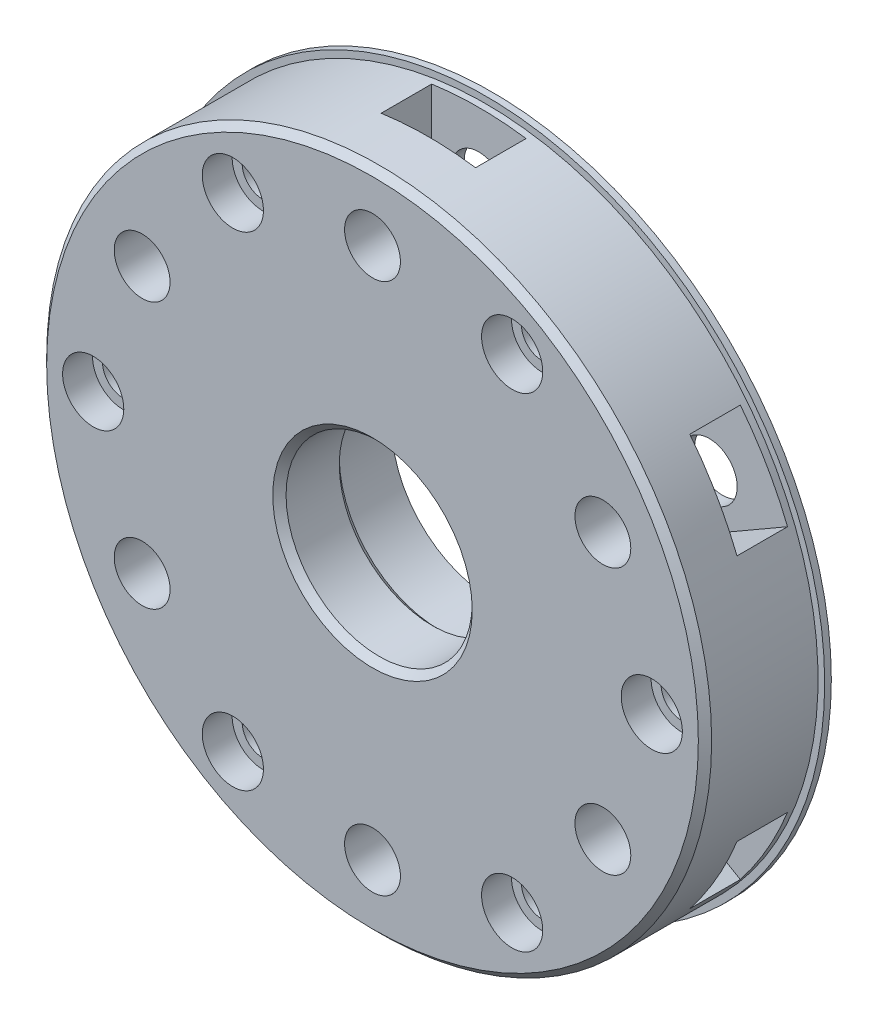
SolidWorks part; units mm, degrees
material "ABS"
ref_plane "Front Plane" through (0, 0, 0) normal (0, 0, 1) x (1, 0, 0)
ref_plane "Top Plane" through (0, 0, 0) normal (0, 1, 0) x (1, 0, 0)
ref_plane "Right Plane" through (0, 0, 0) normal (1, 0, 0) x (0, 0, -1)
sketch "Output Master Sketch" plane through (0, 0, 0) normal (0, 0, 1) x (1, 0, 0)
  circle A0 centre (0, 0) radius 21 construction
  circle A1 centre (21, 0) radius 3.05 construction
  circle A2 centre (10.5, -18.1865) radius 3.05 construction
  circle A3 centre (-10.5, -18.1865) radius 3.05 construction
  circle A4 centre (-21, 0) radius 3.05 construction
  circle A5 centre (-10.5, 18.1865) radius 3.05 construction
  circle A6 centre (10.5, 18.1865) radius 3.05 construction
  circle A7 centre (0, 0) radius 25
  point P17 (0, 0)
extrude "Boss-Extrude1" add sketch "Output Master Sketch" along normal blind 9
sketch "Sketch4" plane through (0, 0, 0) normal (0, 0, 1) x (1, 0, 0)
  circle A0 centre (21, 0) radius 3.05
  circle A1 centre (21, 0) radius 3.05 construction
  circle A2 centre (10.5, -18.1865) radius 3.05
  circle A3 centre (-10.5, -18.1865) radius 3.05
  circle A4 centre (-21, 0) radius 3.05
  circle A5 centre (-10.5, 18.1865) radius 3.05
  circle A6 centre (10.5, 18.1865) radius 3.05
  point P5 (0, 0)
  point P17 (0, 0)
  dimension "D1" = 6
extrude "Cut-Extrude1" cut sketch "Sketch4" along normal blind 4
sketch "Sketch5" plane through (0, 0, 0) normal (0, 0, -1) x (-1, 0, 0)
  circle A0 centre (0, 0) radius 25
  circle A1 centre (0, 0) radius 25.5
  circle A2 centre (0, 0) radius 25 construction
  dimension "D1" = 0.5
extrude "Boss-Extrude2" add sketch "Sketch5" against normal blind 0.5
sketch "Sketch6" plane through (0, 0, 0) normal (0, 0, -1) x (-1, 0, 0)
  circle A0 centre (-21, 0) radius 1.55
  circle A1 centre (-10.5, 18.1865) radius 1.55
  circle A2 centre (10.5, 18.1865) radius 1.55
  circle A3 centre (21, 0) radius 1.55
  circle A4 centre (10.5, -18.1865) radius 1.55
  circle A5 centre (-10.5, -18.1865) radius 1.55
  point P4 (0, 0)
  point P15 (0, 0)
  dimension "D1" = 3.1
  dimension "D2" = 6
extrude "Cut-Extrude2" cut sketch "Sketch6" against normal through all
sketch "Sketch7" plane through (0, 0, 9) normal (0, 0, 1) x (1, 0, 0)
  circle A0 centre (-21, 0) radius 2.3
  circle A1 centre (-10.5, 18.1865) radius 2.3
  circle A2 centre (10.5, 18.1865) radius 2.3
  circle A3 centre (21, 0) radius 2.3
  circle A4 centre (10.5, -18.1865) radius 2.3
  circle A5 centre (-10.5, -18.1865) radius 2.3
  point P3 (0, 0)
  point P16 (0, 0)
  dimension "D1" = 4.6
  dimension "D2" = 6
extrude "Cut-Extrude3" cut sketch "Sketch7" against normal blind 2.25
chamfer "Chamfer1" distance 0.5 angle 45 1 edges at (25, 0, 9)
sketch "Sketch8" plane through (0, 0, 0) normal (0, 0, -1) x (-1, 0, 0)
  circle A0 centre (0, 0) radius 7
  dimension "D1" = 14
extrude "Cut-Extrude4" cut sketch "Sketch8" against normal blind 10
sketch "Sketch9" plane through (0, 0, 0) normal (0, 0, -1) x (-1, 0, 0)
  circle A0 centre (0, 0) radius 7.55
  dimension "D1" = 15.1
extrude "Cut-Extrude5" cut sketch "Sketch9" against normal blind 4
chamfer "Chamfer2" distance 0.5 angle 45 1 edges at (-7, 0, 4)
sketch "Sketch10" plane through (0, 0, 9) normal (0, 0, 1) x (1, 0, 0)
  line L1 (0, 20) -> (-17.3205, 10) construction
  line L2 (-17.3205, 10) -> (-17.3205, -10) construction
  line L3 (-17.3205, -10) -> (0, -20) construction
  line L4 (0, -20) -> (17.3205, -10) construction
  line L5 (17.3205, -10) -> (17.3205, 10) construction
  line L6 (17.3205, 10) -> (0, 20) construction
  circle A0 centre (0, 0) radius 20 construction
  circle A1 centre (0, 20) radius 2.1
  circle A2 centre (17.3205, 10) radius 2.1
  circle A3 centre (17.3205, -10) radius 2.1
  circle A4 centre (0, -20) radius 2.1
  circle A5 centre (-17.3205, -10) radius 2.1
  circle A6 centre (-17.3205, 10) radius 2.1
  point P11 (0, 0)
  point P22 (0, 0)
  dimension "D1" = 40
  dimension "D2" = 4.2
  dimension "D3" = 6
extrude "M4 Thru" cut sketch "Sketch10" against normal through all
chamfer "Chamfer3" distance 0.5 angle 45 1 edges at (7, 0, 9)
sketch "Sketch11" plane through (0, 0, 9) normal (0, 0, 1) x (1, 0, 0)
  line L1 (0, 24.0992) -> (-3.55, 22.0496)
  line L2 (-3.55, 22.0496) -> (-3.55, 17.9504)
  line L3 (-3.55, 17.9504) -> (0, 15.9008)
  line L4 (0, 15.9008) -> (3.55, 17.9504)
  line L5 (3.55, 17.9504) -> (3.55, 22.0496)
  line L6 (3.55, 22.0496) -> (0, 24.0992)
  circle A0 centre (0, 20) radius 3.55 construction
  dimension "D1" = 7.1
extrude "M4 Hexnut Cut" cut sketch "Sketch11" along normal blind 3.8 from offset 8 offset against normal yes
ref_plane "Plane2" through (0, 22.0496, 0) normal (0, 1, 0) x (1, 0, 0)
sketch "Sketch12" plane through (0, 22.0496, 0) normal (0, 1, 0) x (1, 0, 0)
  line L1 (-3.55, -1) -> (3.55, -1)
  line L2 (-3.55, -1) -> (-3.55, -4.8)
  line L3 (-3.55, -4.8) -> (3.55, -4.8)
  line L4 (3.55, -1) -> (3.55, -4.8)
extrude "M4 Hexnut Slot" cut sketch "Sketch12" along normal through all contours L2 L1 L4 L3
pattern_circular "M4 Hexnut Pattern" count 6 over 360 about axis through (0, 0, 10) along (0, 0, -1) of "M4 Hexnut Cut", "M4 Hexnut Slot" reverse direction yes
